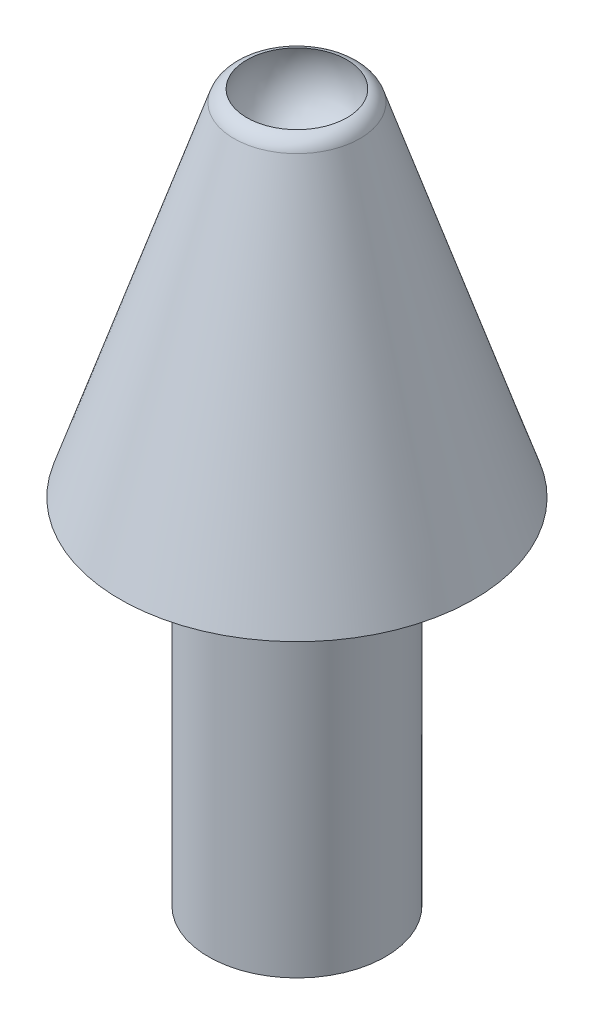
SolidWorks part; units mm, degrees
ref_plane "Alzado" through (0, 0, 0) normal (0, 0, 1) x (1, 0, 0)
ref_plane "Planta" through (0, 0, 0) normal (0, 1, 0) x (1, 0, 0)
ref_plane "Vista lateral" through (0, 0, 0) normal (1, 0, 0) x (0, 0, -1)
sketch "Croquis1" plane through (0, 0, 0) normal (0, 0, 1) x (1, 0, 0)
  line L0 (0.4, -1.4201) -> (0.4, 0.6799)
  line L1 (0.5, -1.4201) -> (0.5, 0.5799)
  line L2 (0.5, 0.5799) -> (1, 0.5799)
  line L3 (1, 0.5799) -> (0.3342, 2.5799)
  line L4 (0.3342, 2.5799) -> (0.2834, 2.5799)
  line L5 (0, -1000) -> (0, 2.2035) construction
  line L6 (0.4, 0.6799) -> (0.1, 0.6799)
  line L7 (0.1, 0.6799) -> (0.1, 2.1985)
  line L8 (0.8613, 0.6799) -> (0.2612, 2.4826) construction
  line L9 (0.4, -1.4201) -> (0.5, -1.4201)
  line L10 (0.3342, 2.5799) -> (0.2842, 2.5799) construction
  line L11 (0.2612, 2.4826) -> (0.2612, 2.4826) construction
  line L12 (0.4, 0.6799) -> (0.8613, 0.6799) construction
  arc A0 (0.1, 2.1985) -> (0.2834, 2.5799) centre (0, 2.4814) ccw
  dimension "D7" = 0.3
  dimension "D1" = 0.5
  dimension "D2" = 0.5
  dimension "D3" = 2
  dimension "D4" = 0.0508
  dimension "D5" = 0.3
  dimension "D6" = 2
revolve "Revolución1" add sketch "Croquis1" angle 360 about L5
fillet "Redondeo1" radius 0.1 1 edges at (0, 2.5799, -0.3342)
